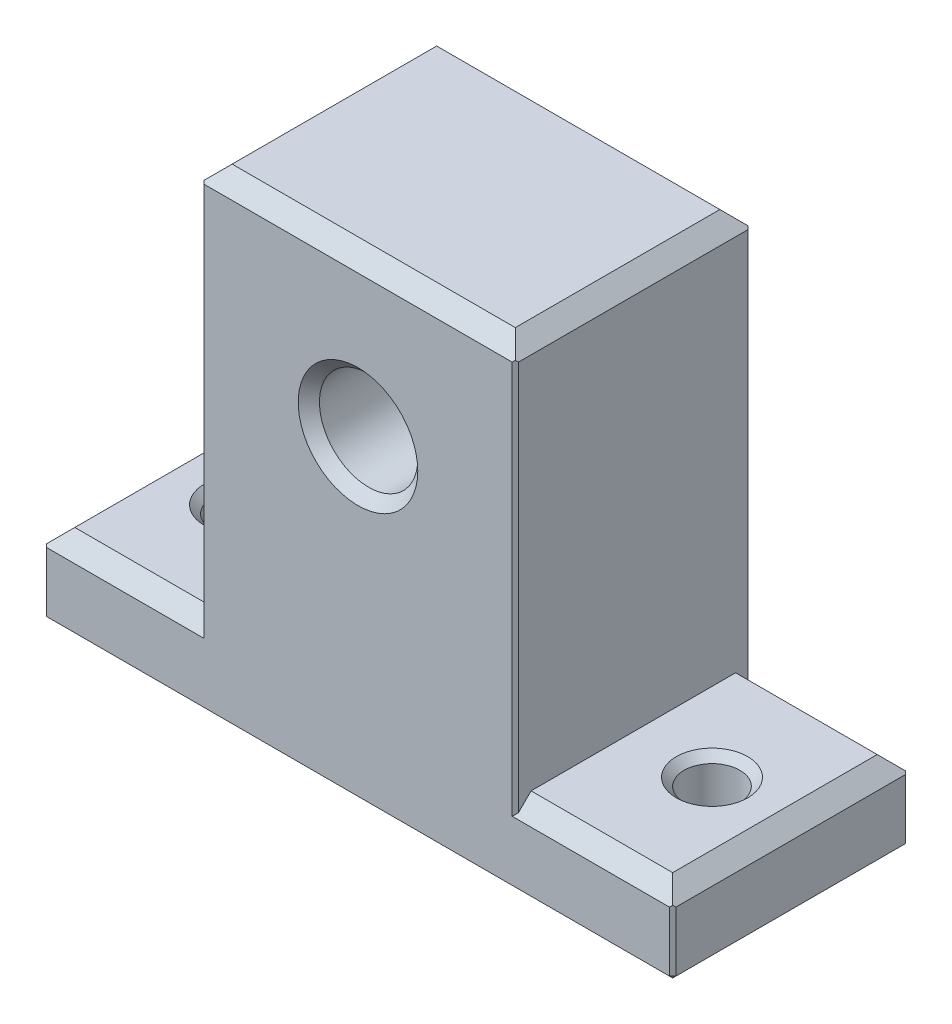
SolidWorks part; units mm, degrees
material "6061-T6 (SS)"
ref_plane "Front Plane" through (0, 0, 0) normal (0, 0, 1) x (1, 0, 0)
ref_plane "Top Plane" through (0, 0, 0) normal (0, 1, 0) x (1, 0, 0)
ref_plane "Right Plane" through (0, 0, 0) normal (1, 0, 0) x (0, 0, -1)
ref_axis "X Axis" through (88.99, 0, 0) along (-1, 0, 0)
ref_axis "Y Axis" through (0, 55, 0) along (0, -1, 0)
ref_axis "Z Axis" through (0, 0, -88.99) along (0, 0, 1)
sketch "Sketch1" plane through (0, 0, 0) normal (0, 1, 0) x (1, 0, 0)
  line L1 (-25.4, -9.525) -> (25.4, -9.525)
  line L2 (-25.4, -9.525) -> (-25.4, 9.525)
  line L3 (-25.4, 9.525) -> (25.4, 9.525)
  line L4 (25.4, -9.525) -> (25.4, 9.525)
  line L5 (0, 9.525) -> (0, -9.525) construction
  line L6 (-25.4, 0) -> (25.4, 0) construction
  line L7 (-12.7, -9.525) -> (12.7, -9.525)
  line L8 (-12.7, -9.525) -> (-12.7, 9.525)
  line L9 (-12.7, 9.525) -> (12.7, 9.525)
  line L10 (12.7, -9.525) -> (12.7, 9.525)
  line L11 (0, 9.525) -> (0, -9.525) construction
  line L12 (-12.7, 0) -> (12.7, 0) construction
  point P0 (0, 0)
  point P4 (0, 0)
  dimension "D1" = 19.05
  dimension "D2" = 50.8
  dimension "D3" = 25.4
extrude "Boss-Extrude1" add sketch "Sketch1" along normal blind 6.35 contours L1 L8 L3 L2 | L1 L10 L3 L8 | L10 L1 L4 L3 region at (-19.05, 0, 0) region at (0, 0, 0) region at (19.05, 0, 0)
extrude "Boss-Extrude2" add sketch "Sketch1<3>" along normal blind 38.1 contours L1 L10 L3 L8 region at (0, 0, 0)
sketch "Sketch1<3>" plane through (0, 0, 0) normal (0, 1, 0) x (1, 0, 0) same geometry as "Sketch1"
sketch "Sketch3" plane through (0, 0, 9.525) normal (0, 0, 1) x (1, 0, 0)
  line L0 (0, 0) -> (0, 25.4) construction
  point P1 (0, 25.4)
  point P13 (0, 25.4)
  point P16 (0, 0)
  dimension "D1" = 25.4
hole_wizard "3/8-16 Tapped Hole1" positions "Sketch3" profile "Sketch4" tap size "3/8-16" standard "ANSI Inch" end condition through all
sketch "Sketch4" plane through (0, 25.4, 9.525) normal (1, 0, 0) x (0, -1, 0)
  line L0 (0, 0) -> (0, 19.05)
  line L1 (0, 19.05) -> (4.826, 19.05)
  line L2 (3.9687, 18.1927) -> (3.9687, 0.8573)
  line L3 (3.9687, 0.8573) -> (4.826, 0)
  line L5 (4.826, 0) -> (0, 0)
  line L6 (-3.9687, 0.8572) -> (-4.826, 0) construction
  line L7 (4.826, 19.05) -> (3.9687, 18.1927)
  line L8 (-4.826, 19.05) -> (-3.9688, 18.1927) construction
  line L11 (0, -6.35) -> (0, 107.95) construction
  dimension "Thru Tap Drill Dia." = 7.9375
  dimension "Thru Tap Drill Depth" = 19.05
  dimension "Near C'Sink Dia." = 9.652
  dimension "Near C'Sink Angle" = 90
  dimension "Far C'Sink Dia." = 9.652
  dimension "Far C'Sink Angle" = 90
cosmetic thread "Hole Thread1" parameters "D2"=9.525
sketch "Sketch6" plane through (0, 38.1, 0) normal (0, 1, 0) x (1, 0, 0)
  line L0 (19.05, 0) -> (-19.05, 0)
  point P4 (0, 0)
  dimension "D1" = 38.1
sketch "Sketch9" plane through (0, 6.35, 0) normal (0, 1, 0) x (1, 0, 0)
  point P0 (-19.05, 0)
  point P3 (19.05, 0)
hole_wizard "#8 Clearance Hole1" positions "Sketch9" profile "Sketch8" hole size "#8" standard "ANSI Inch" end condition through all
sketch "Sketch8" plane through (-19.05, 6.35, 0) normal (1, 0, 0) x (0, 0, 1)
  line L0 (0, 0) -> (0, 6.35)
  line L1 (0, 6.35) -> (2.8829, 6.35)
  line L2 (2.2479, 5.715) -> (2.2479, 0.635)
  line L3 (2.2479, 0.635) -> (2.8829, 0)
  line L5 (2.8829, 0) -> (0, 0)
  line L6 (-2.2479, 0.635) -> (-2.8829, 0) construction
  line L7 (2.8829, 6.35) -> (2.2479, 5.715)
  line L8 (-2.8829, 6.35) -> (-2.2479, 5.715) construction
  line L11 (0, -6.35) -> (0, 107.95) construction
  dimension "Thru Hole Dia." = 4.4958
  dimension "Thru Hole Depth" = 6.35
  dimension "Near C'Sink Dia." = 5.7658
  dimension "Near C'Sink Angle" = 90
  dimension "Far C'Sink Dia." = 5.7658
  dimension "Far C'Sink Angle" = 90
chamfer "Chamfer1" distance 1.27 angle 45 10 edges at (-12.7, 38.1, 0) (0, 38.1, -9.525) (12.7, 38.1, 0) (0, 38.1, 9.525) (19.05, 6.35, -9.525) (25.4, 6.35, 0) (19.05, 6.35, 9.525) (-19.05, 6.35, -9.525) (-19.05, 6.35, 9.525) (-25.4, 6.35, 0)
chamfer "Chamfer2" distance 0.254 angle 45 12 edges at (25.4, 2.54, -9.525) (25.4, 2.54, 9.525) (-25.4, 2.54, -9.525) (-25.4, 2.54, 9.525) (-25.4, 0, 0) (0, 0, -9.525) (25.4, 0, 0) (0, 0, 9.525) (12.7, 20.955, -9.525) (12.7, 20.955, 9.525) (-12.7, 20.955, 9.525) (-12.7, 20.955, -9.525)
ref_axis "Hole Axis" through (0, 25.4, -34.9674) along (0, 0, 1)
